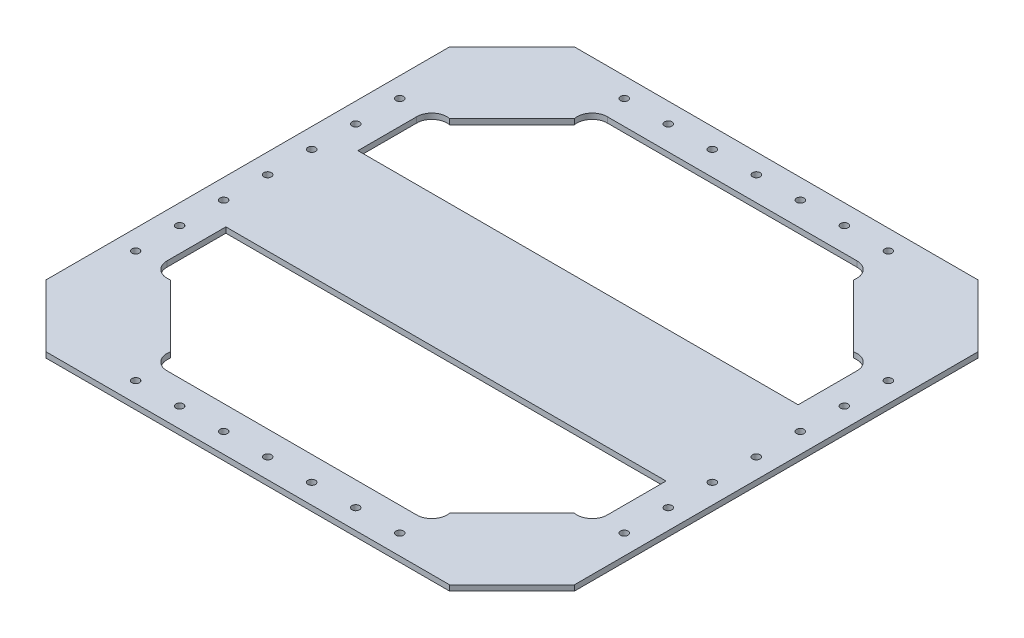
SolidWorks part; units mm, degrees
ref_plane "Front Plane" through (0, 0, 0) normal (0, 0, 1) x (1, 0, 0)
ref_plane "Top Plane" through (0, 0, 0) normal (0, 1, 0) x (1, 0, 0)
ref_plane "Right Plane" through (0, 0, 0) normal (1, 0, 0) x (0, 0, -1)
sketch "Sketch1" plane through (0, 0, 0) normal (0, 1, 0) x (1, 0, 0)
  line L0 (-152.4, 68.2596) -> (-116.479, 104.1807)
  line L1 (-116.479, 104.1807) -> (116.479, 104.1807)
  line L2 (-152.4, 68.2596) -> (-152.4, -164.6983)
  line L3 (152.4, 68.2596) -> (152.4, -164.6983)
  line L4 (152.4, 68.2596) -> (116.479, 104.1807)
  line L5 (0, 104.1807) -> (0, -200.6193) construction
  line L6 (-152.4, -48.2193) -> (152.4, -48.2193) construction
  line L7 (152.4, -164.6983) -> (116.479, -200.6193)
  line L8 (-116.479, -200.6193) -> (116.479, -200.6193)
  line L9 (-152.4, -164.6983) -> (-116.479, -200.6193)
  point P9 (0, -48.2193)
  point P11 (0, -48.2193)
  point P15 (0, 0)
  dimension "D3" = 50.8
  dimension "D4" = 135
extrude "Boss-Extrude1" add sketch "Sketch1" along normal blind 3.175
sketch "Sketch2" plane through (0, 3.175, 0) normal (0, 1, 0) x (1, 0, 0)
  line L0 (-152.4, -48.2193) -> (199.0625, -48.2193) construction
  line L1 (-152.4, 68.2596) -> (-152.4, -164.6983) construction
  line L2 (-91.079, 78.7807) -> (91.079, 78.7807)
  line L4 (82.443, -10.1193) -> (-74.315, -10.1193)
  line L6 (-116.479, 104.1807) -> (-91.079, 78.7807) construction
  line L7 (116.479, 104.1807) -> (91.079, 78.7807) construction
  line L8 (116.479, 104.1807) -> (-116.479, 104.1807) construction
  line L9 (-74.315, -10.1193) -> (-127, -10.1193)
  line L10 (-127, -10.1193) -> (-127, 42.8596)
  line L11 (-127, 42.8596) -> (-91.079, 78.7807)
  line L12 (82.443, -10.1193) -> (127, -10.1193)
  line L13 (127, -10.1193) -> (127, 42.8596)
  line L14 (127, 42.8596) -> (91.079, 78.7807)
  line L16 (127, -139.2983) -> (91.079, -175.2193)
  line L17 (127, -86.3193) -> (127, -139.2983)
  line L18 (82.443, -86.3193) -> (127, -86.3193)
  line L19 (-127, -139.2983) -> (-91.079, -175.2193)
  line L20 (-127, -86.3193) -> (-127, -139.2983)
  line L21 (-74.315, -86.3193) -> (-127, -86.3193)
  line L23 (82.443, -86.3193) -> (-74.315, -86.3193)
  line L25 (-91.079, -175.2193) -> (91.079, -175.2193)
  dimension "D1" = 135
  dimension "D2" = 135
  dimension "D3" = 25.4
  dimension "D4" = 90
  dimension "D5" = 90
  dimension "D6" = 50.8
  dimension "D7" = 50.8
  dimension "D8" = 38.1
  dimension "D9" = 25.4
extrude "Cut-Extrude1" cut sketch "Sketch2" against normal through all
sketch "Sketch4" plane through (0, 3.175, 0) normal (0, 1, 0) x (1, 0, 0)
  line L0 (-152.4, -48.2193) -> (171.6111, -48.2193) construction
  line L1 (-152.4, 68.2596) -> (-152.4, -164.6983) construction
  line L2 (116.479, 104.1807) -> (-116.479, 104.1807) construction
  line L4 (152.4, -164.6983) -> (152.4, 68.2596) construction
  circle A0 centre (0, 92.7507) radius 2.159
  circle A1 centre (-50.8, 92.7507) radius 2.159
  circle A2 centre (50.8, 92.7507) radius 2.159
  circle A3 centre (-25.4, 92.7507) radius 2.159
  circle A4 centre (25.4, 92.7507) radius 2.159
  circle A5 centre (-140.97, -48.2193) radius 2.159
  circle A6 centre (-140.97, -22.8193) radius 2.159
  circle A7 centre (-140.97, 2.5807) radius 2.159
  circle A8 centre (140.97, -48.2193) radius 2.159
  circle A9 centre (140.97, -22.8193) radius 2.159
  circle A10 centre (140.97, 2.5807) radius 2.159
  circle A11 centre (140.97, -99.0193) radius 2.159
  circle A12 centre (140.97, -73.6193) radius 2.159
  circle A13 centre (-140.97, -99.0193) radius 2.159
  circle A14 centre (-140.97, -73.6193) radius 2.159
  circle A15 centre (25.4, -189.1893) radius 2.159
  circle A16 centre (-25.4, -189.1893) radius 2.159
  circle A17 centre (50.8, -189.1893) radius 2.159
  circle A18 centre (-50.8, -189.1893) radius 2.159
  circle A19 centre (0, -189.1893) radius 2.159
  circle A20 centre (-76.2, 92.7507) radius 2.159
  circle A21 centre (76.2, 92.7507) radius 2.159
  circle A22 centre (-140.97, 27.9807) radius 2.159
  circle A23 centre (140.97, 27.9807) radius 2.159
  circle A24 centre (140.97, -124.4193) radius 2.159
  circle A25 centre (76.2, -189.1893) radius 2.159
  circle A26 centre (-76.2, -189.1893) radius 2.159
  circle A27 centre (-140.97, -124.4193) radius 2.159
  point P48 (0, 104.1807)
  point P56 (0, 0)
  point P57 (0, 0)
  dimension "D1" = 4.318
  dimension "D2" = 4.318
  dimension "D3" = 4.318
  dimension "D4" = 4.318
  dimension "D5" = 4.318
  dimension "D6" = 4.318
  dimension "D7" = 4.318
  dimension "D8" = 4.318
  dimension "D9" = 4.318
  dimension "D10" = 4.318
  dimension "D11" = 4.318
  dimension "D23" = 4.318
  dimension "D24" = 4.318
  dimension "D27" = 4.318
  dimension "D28" = 4.318
  dimension "D12" = 25.4
  dimension "D13" = 25.4
  dimension "D14" = 25.4
  dimension "D15" = 25.4
  dimension "D16" = 25.4
  dimension "D17" = 25.4
  dimension "D18" = 25.4
  dimension "D19" = 25.4
  dimension "D20" = 11.43
  dimension "D21" = 11.43
  dimension "D22" = 11.43
  dimension "D25" = 25.4
  dimension "D26" = 25.4
  dimension "D29" = 25.4
  dimension "D30" = 25.4
sketch "Sketch5" plane through (0, 3.175, 0) normal (0, 1, 0) x (1, 0, 0)
  line L0 (-116.479, 32.3386) -> (-80.558, 68.2596)
  line L1 (0, 78.7807) -> (0, -138.0704) construction
  line L3 (-152.4, 68.2596) -> (-152.4, 11.1096)
  line L4 (-127, 42.8596) -> (-127, -10.1193) construction
  line L5 (91.079, 78.7807) -> (-91.079, 78.7807) construction
  line L6 (-116.479, 104.1807) -> (-59.329, 104.1807)
  line L7 (116.479, 104.1807) -> (-116.479, 104.1807) construction
  line L8 (-59.329, 104.1807) -> (-59.329, 78.7807)
  line L9 (-152.4, 68.2596) -> (-116.479, 104.1807)
  line L10 (-152.4, 68.2596) -> (-152.4, -164.6983) construction
  line L12 (-152.4, 11.1096) -> (-127, 11.1096)
  line L13 (-59.329, 78.7807) -> (-72.029, 78.7807)
  line L14 (127, 11.1096) -> (127, 23.8096)
  line L15 (152.4, -48.2193) -> (-208.2375, -48.2193) construction
  line L16 (152.4, -164.6983) -> (152.4, 68.2596) construction
  line L17 (59.329, 78.7807) -> (72.029, 78.7807)
  line L18 (-127, 11.1096) -> (-127, 23.8096)
  line L19 (152.4, 11.1096) -> (127, 11.1096)
  line L20 (152.4, 68.2596) -> (116.479, 104.1807)
  line L21 (59.329, 104.1807) -> (59.329, 78.7807)
  line L22 (116.479, 104.1807) -> (59.329, 104.1807)
  line L24 (152.4, 68.2596) -> (152.4, 11.1096)
  line L25 (116.479, 32.3386) -> (80.558, 68.2596)
  line L26 (116.479, -128.7773) -> (80.558, -164.6983)
  line L27 (152.4, -164.6983) -> (152.4, -107.5483)
  line L28 (116.479, -200.6193) -> (59.329, -200.6193)
  line L29 (59.329, -200.6193) -> (59.329, -175.2193)
  line L30 (152.4, -164.6983) -> (116.479, -200.6193)
  line L31 (152.4, -107.5483) -> (127, -107.5483)
  line L32 (-127, -107.5483) -> (-127, -120.2483)
  line L33 (59.329, -175.2193) -> (72.029, -175.2193)
  line L34 (127, -107.5483) -> (127, -120.2483)
  line L35 (-59.329, -175.2193) -> (-72.029, -175.2193)
  line L36 (-152.4, -107.5483) -> (-127, -107.5483)
  line L37 (-152.4, -164.6983) -> (-116.479, -200.6193)
  line L38 (-59.329, -200.6193) -> (-59.329, -175.2193)
  line L39 (-116.479, -200.6193) -> (-59.329, -200.6193)
  line L40 (-152.4, -164.6983) -> (-152.4, -107.5483)
  line L41 (-116.479, -128.7773) -> (-80.558, -164.6983)
  arc A0 (-72.029, 78.7807) -> (-80.558, 68.2596) centre (-72.029, 70.0631) ccw
  arc A1 (-127, 23.8096) -> (-116.479, 32.3386) centre (-118.2824, 23.8096) cw
  arc A2 (127, 23.8096) -> (116.479, 32.3386) centre (118.2824, 23.8096) ccw
  arc A3 (72.029, 78.7807) -> (80.558, 68.2596) centre (72.029, 70.0631) cw
  arc A4 (72.029, -175.2193) -> (80.558, -164.6983) centre (72.029, -166.5018) ccw
  arc A5 (127, -120.2483) -> (116.479, -128.7773) centre (118.2824, -120.2483) cw
  arc A6 (-127, -120.2483) -> (-116.479, -128.7773) centre (-118.2824, -120.2483) ccw
  arc A7 (-72.029, -175.2193) -> (-80.558, -164.6983) centre (-72.029, -166.5018) cw
  dimension "D3" = 12.7
  dimension "D1" = 50.8
  dimension "D2" = 50.8
  dimension "D4" = 12.7
  dimension "D5" = 57.15
  dimension "D6" = 57.15
extrude "Boss-Extrude2" add sketch "Sketch5" against normal blind 3.175
extrude "Cut-Extrude2" cut sketch "Sketch4" against normal through all
